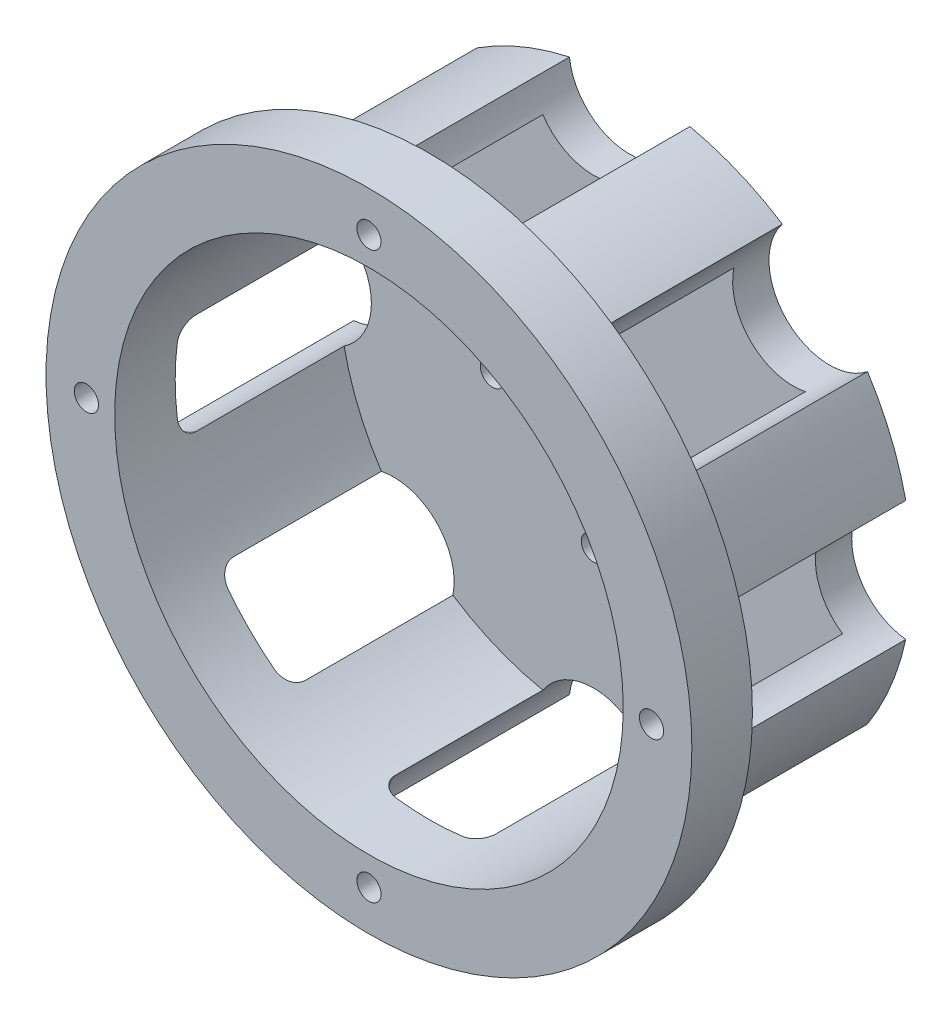
SolidWorks part; units mm, degrees
material "ABS PC"
ref_plane "Front Plane" through (0, 0, 0) normal (0, 0, 1) x (1, 0, 0)
ref_plane "Top Plane" through (0, 0, 0) normal (0, 1, 0) x (1, 0, 0)
ref_plane "Right Plane" through (0, 0, 0) normal (1, 0, 0) x (0, 0, -1)
sketch "Sketch1" plane through (0, 0, 0) normal (0, 0, 1) x (1, 0, 0)
  circle A0 centre (0, 0) radius 31.5
  circle A1 centre (0, 0) radius 35
  circle A2 centre (0, 0) radius 7
  circle A3 centre (0, 0) radius 12.5
  circle A4 centre (0, 12.5) radius 1.5
  circle A5 centre (12.5, 0) radius 1.5
  circle A6 centre (0, -12.5) radius 1.5
  circle A7 centre (-12.5, 0) radius 1.5
  point P17 (0, 0)
  dimension "D1" = 63
  dimension "D2" = 70
  dimension "D3" = 14
  dimension "D4" = 25
  dimension "D5" = 3
  dimension "D6" = 4
extrude "Boss-Extrude1" add sketch "Sketch1" along normal blind 4.5 contours A0 A7 A3 A4 A5 A6 | A7 A3 A6 A5 A4 A2 region at (-30.609, 0, 0) region at (10.649, 0, 0)
extrude "Boss-Extrude2" add sketch "Sketch1<3>" along normal blind 32.3 contours A1 A0 region at (-34.0101, 0, 0)
sketch "Sketch1<3>" plane through (0, 0, 0) normal (0, 0, 1) x (1, 0, 0) same geometry as "Sketch1"
sketch "Sketch2" plane through (0, 0, 0) normal (0, 0, -1) x (-1, 0, 0)
  circle A0 centre (0, 35) radius 7.5
  circle A1 centre (0, 0) radius 35 construction
  circle A2 centre (24.7487, 24.7487) radius 7.5
  circle A3 centre (35, 0) radius 7.5
  circle A4 centre (24.7487, -24.7487) radius 7.5
  circle A5 centre (0, -35) radius 7.5
  circle A6 centre (-24.7487, -24.7487) radius 7.5
  circle A7 centre (-35, 0) radius 7.5
  circle A8 centre (-24.7487, 24.7487) radius 7.5
  point P20 (0, 0)
  dimension "D1" = 15
  dimension "D2" = 8
extrude "Cut-Extrude1" cut sketch "Sketch2" against normal blind 27.5
sketch "Sketch3" plane through (0, 0, 32.3) normal (0, 0, 1) x (1, 0, 0)
  circle A0 centre (0, 0) radius 40
  circle A1 centre (0, 0) radius 31.5
  dimension "D1" = 80
  dimension "D2" = 63
extrude "Boss-Extrude3" add sketch "Sketch3" against normal blind 7.5
sketch "Sketch4" plane through (0, 0, 32.3) normal (0, 0, 1) x (1, 0, 0)
  circle A0 centre (0, 35) radius 1.5
  circle A1 centre (35, 0) radius 1.5
  circle A2 centre (0, -35) radius 1.5
  circle A3 centre (-35, 0) radius 1.5
  point P13 (0, 0)
  dimension "D1" = 3
  dimension "D2" = 4
extrude "Cut-Extrude2" cut sketch "Sketch4" against normal blind 10
fillet "Fillet1" radius 2 24 edges at (-32.4625, -7.0577, 24.8) (27.945, 17.9639, 24.8) (-27.945, 17.9639, 24.8) (-7.0577, 32.4625, 24.8) (17.9639, 27.945, 24.8) (32.4625, -7.0577, 24.8) (32.4625, 7.0577, 24.8) (-17.9639, -27.945, 24.8) (7.0577, -32.4625, 24.8) (27.945, -17.9639, 24.8) (17.9639, -27.945, 24.8) (-7.0577, -32.4625, 24.8) (-27.945, -17.9639, 24.8) (-32.4625, 7.0577, 24.8) (-17.9639, 27.945, 24.8) (7.0577, 32.4625, 24.8) (13.3939, 32.3358, 24.8) (32.3358, 13.3939, 24.8) (32.3358, -13.3939, 24.8) (13.3939, -32.3358, 24.8) (-13.3939, -32.3358, 24.8) (-32.3358, -13.3939, 24.8) (-32.3358, 13.3939, 24.8) (-13.3939, 32.3358, 24.8)
